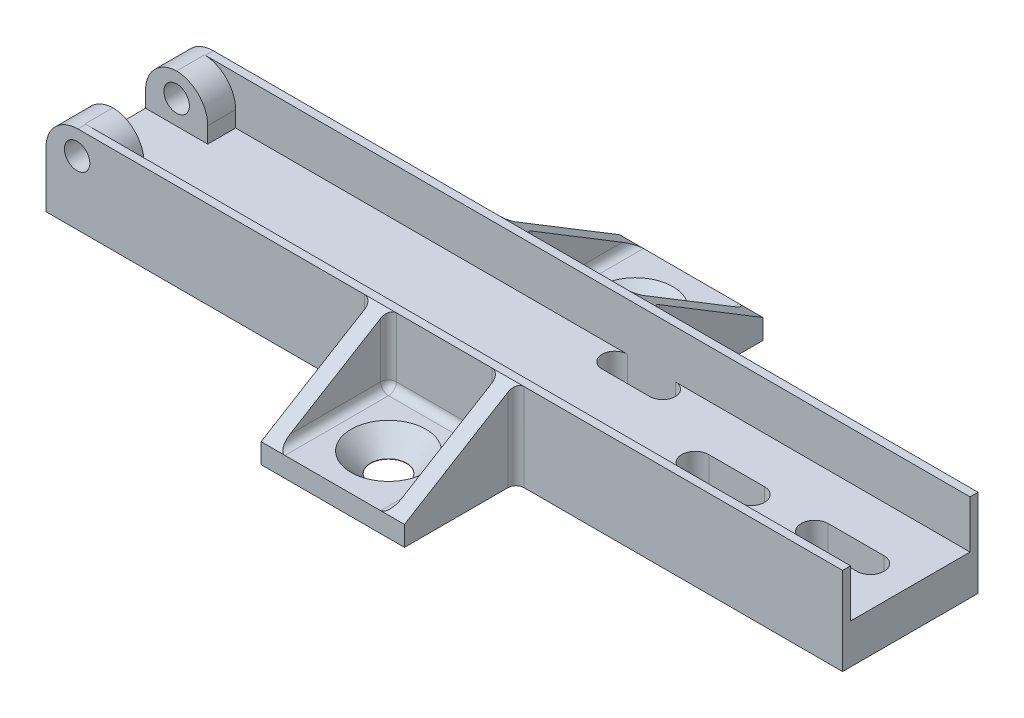
SolidWorks part; units mm, degrees
ref_plane "Ebene vorne" through (0, 0, 0) normal (0, 0, 1) x (1, 0, 0)
ref_plane "Ebene oben" through (0, 0, 0) normal (0, 1, 0) x (1, 0, 0)
ref_plane "Ebene rechts" through (0, 0, 0) normal (1, 0, 0) x (0, 0, -1)
sketch "Sketch1" plane through (0, 0, 0) normal (0, 1, 0) x (1, 0, 0)
  line L0 (-50, -7.5) -> (-50, 7.5)
  line L1 (-50, -7.5) -> (50, -7.5)
  line L2 (-50, 7.5) -> (50, 7.5)
  line L3 (50, -7.5) -> (50, 7.5)
  line L4 (-50, -7.5) -> (50, 7.5) construction
  line L5 (-50, 7.5) -> (50, -7.5) construction
  point P1 (0, 0)
  dimension "D1" = 15
  dimension "D2" = 100
extrude "Boss-Extrude1" add sketch "Sketch1" along normal blind 5
sketch "Sketch2" plane through (0, 5, 0) normal (0, 1, 0) x (1, 0, 0)
  line L0 (-50, -7.5) -> (50, -7.5) construction
  line L1 (-50, 7.5) -> (-42.1952, 7.5)
  line L2 (-50, 7.5) -> (-50, -7.5)
  line L3 (-50, -7.5) -> (-42.1952, -7.5)
  line L4 (-42.1952, 7.5) -> (-42.1952, -7.5)
extrude "Boss-Extrude2" add sketch "Sketch2" along normal blind 6
fillet "Fillet1" radius 4 1 edges at (-42.1952, 11, 0)
sketch "Sketch4" plane through (0, 11, 0) normal (0, 1, 0) x (1, 0, 0)
  line L0 (-42.1952, 0) -> (-50, 0) construction
  line L1 (-42.1952, -7.5) -> (-42.1952, 7.5) construction
  line L2 (-50, 7.5) -> (-50, -7.5) construction
  line L3 (-50, -4) -> (-42.1952, -4)
  line L4 (-50, -4) -> (-50, 4)
  line L5 (-42.1952, -4) -> (-42.1952, 4)
  line L6 (-50, 4) -> (-42.1952, 4)
  line L7 (-50, -4) -> (-42.1952, 4) construction
  line L8 (-42.1952, -4) -> (-50, 4) construction
  point P7 (-46.0976, 0)
  dimension "D1" = 8
extrude "Cut-Extrude2" cut sketch "Sketch4" against normal up to surface (6 mm away) up to face at (3.9024, 5, 0)
sketch "Sketch5" plane through (0, 0, 0) normal (0, -1, 0) x (1, 0, 0)
  line L0 (45, 0) -> (38, 0) construction
  line L1 (45, -1.7) -> (38, -1.7)
  line L2 (45, 1.7) -> (38, 1.7)
  line L3 (30, 0) -> (23, 0) construction
  line L4 (30, -1.7) -> (23, -1.7)
  line L5 (30, 1.7) -> (23, 1.7)
  line L7 (50, 7.5) -> (50, -7.5) construction
  arc A0 (45, -1.7) -> (45, 1.7) centre (45, 0) ccw
  arc A1 (38, 1.7) -> (38, -1.7) centre (38, 0) ccw
  arc A2 (30, -1.7) -> (30, 1.7) centre (30, 0) ccw
  arc A3 (23, 1.7) -> (23, -1.7) centre (23, 0) ccw
  point P3 (41.5, 0)
  point P8 (26.5, 0)
  dimension "D2" = 15
  dimension "^3,4" = 3.4
  dimension "D3" = 3.4
  dimension "D4" = 5
  dimension "D5" = 7
  dimension "D6" = 7
extrude "Cut-Extrude3" cut sketch "Sketch5" against normal up to surface (5 mm away) up to face at (-21.0976, 5, 0)
sketch "Sketch6" plane through (0, 5, 0) normal (0, 1, 0) x (1, 0, 0)
  line L0 (-50, 4) -> (-50, -4) construction
  line L1 (-26, 7.5) -> (-26, -7.5) construction
  line L2 (50, 7.5) -> (-42.1952, 7.5) construction
  line L3 (-42.1952, -7.5) -> (50, -7.5) construction
  circle A0 centre (-26, 0) radius 2.5
  point P10 (-26, 0)
  dimension "D1" = 5
  dimension "D2" = 24
extrude "Boss-Extrude3" [suppressed] add sketch "Sketch6" along normal blind 15
sketch "Sketch8" plane through (0, 0, 7.5) normal (0, 0, 1) x (1, 0, 0)
  line L1 (50, 0) -> (-50, 0)
  line L2 (50, 0) -> (50, 11)
  line L3 (50, 11) -> (-50, 11)
  line L4 (-50, 0) -> (-50, 11)
extrude "Boss-Extrude5" add sketch "Sketch8" along normal blind 1
mirror "Mirror1" about plane through (0, 0, 0) normal (0, 0, 1) of "Boss-Extrude5"
sketch "Sketch3" plane through (0, 0, 8.5) normal (0, 0, 1) x (1, 0, 0)
  line L0 (-42.1952, 7) -> (-42.1952, 5) construction
  line L1 (-42.1952, 8) -> (-50, 8) construction
  line L4 (-42.1952, 7) -> (-42.1952, 5) construction
  line L5 (-42.1952, 5) -> (-42.1952, 11) construction
  line L6 (50, 11) -> (-50, 11) construction
  line L7 (-50, 11) -> (-50, 0) construction
  circle A0 centre (-46.0976, 8) radius 1.6
  arc A1 (-42.1952, 7) -> (-46.1952, 11) centre (-46.1952, 7) ccw construction
  arc A2 (-42.1952, 7) -> (-46.1952, 11) centre (-46.1952, 7) ccw construction
  point P4 (0, 0)
  point P5 (0, 0)
  point P6 (0, 0)
  point P11 (0, 0)
  dimension "D1" = 3.2
extrude "Cut-Extrude1" cut sketch "Sketch3" against normal through all
fillet "Fillet2" radius 4 2 edges at (-50, 11, 6.25) (-50, 11, -6.25)
sketch "Sketch9" plane through (0, 0, 8.5) normal (0, 0, 1) x (1, 0, 0)
  line L0 (-50, 0) -> (50, 0) construction
  line L1 (-9, 0) -> (9, 0)
  line L2 (-9, 0) -> (-9, 2.5)
  line L3 (-9, 2.5) -> (9, 2.5)
  line L4 (9, 0) -> (9, 2.5)
  dimension "D1" = 2.5
  dimension "D2" = 18
extrude "Boss-Extrude6" add sketch "Sketch9" along normal blind 14
ref_plane "Plane1" through (0, 0, 0) normal (-1, 0, 0) x (0, 0, 1)
sketch "Sketch10" plane through (9, 0, 0) normal (1, 0, 0) x (0, 0, -1)
  line L0 (-8.5, 11) -> (-22.5, 2.5)
  line L1 (-22.5, 2.5) -> (-8.5, 2.5) construction
  line L2 (-22.5, 2.5) -> (-8.5, 2.5)
  line L3 (-8.5, 0) -> (-8.5, 11) construction
  line L4 (-8.5, 2.5) -> (-8.5, 11)
extrude "Boss-Extrude7" add sketch "Sketch10" against normal blind 2
mirror "Mirror2" about plane through (0, 0, 0) normal (-1, 0, 0) of "Boss-Extrude7"
hole_wizard "CSK for M4 Countersunk Flat Head Screw1" positions "Sketch13" profile "Sketch12" countersink size "M4" standard "DIN" end condition up to next
sketch "Sketch13" plane through (0, 2.5, 0) normal (0, 1, 0) x (1, 0, 0)
  line L0 (7, -15.5) -> (-7, -15.5) construction
  line L1 (7, -22.5) -> (7, -8.5) construction
  line L2 (-7, -22.5) -> (-7, -8.5) construction
  point P9 (0, -15.5)
sketch "Sketch12" plane through (0, 2.5, 15.5) normal (1, 0, 0) x (0, 0, 1)
  line L0 (0, 0) -> (0, 2.501)
  line L1 (0, 2.501) -> (2.25, 2.501)
  line L2 (2.25, 2.501) -> (2.25, 2.45)
  line L3 (2.25, 2.45) -> (4.7, 0)
  line L5 (4.7, 0) -> (0, 0)
  line L6 (-2.25, 2.45) -> (-4.7, 0) construction
  line L11 (0, -6.35) -> (0, 107.95) construction
  dimension "Thru Hole Dia." = 4.5
  dimension "Thru Hole Depth" = 2.501
  dimension "Near C'Sink Dia." = 9.4
  dimension "Near C'Sink Angle" = 90
mirror "Mirror5" about plane through (0, 0, 0) normal (0, 0, 1) of "CSK for M4 Countersunk Flat Head Screw1", "Mirror2", "Boss-Extrude7", "Boss-Extrude6"
fillet "Fillet4" radius 1 14 edges at (-7, 6.75, 8.5) (7, 6.75, 8.5) (9, 5.5, 8.5) (-9, 5.5, 8.5) (-7, 2.5, 15.5) (7, 2.5, 15.5) (0, 2.5, 8.5) (9, 5.5, -8.5) (-9, 5.5, -8.5) (7, 6.75, -8.5) (-7, 6.75, -8.5) (0, 2.5, -8.5) (-7, 2.5, -15.5) (7, 2.5, -15.5)
sketch "Sketch14" plane through (0, 5, 0) normal (0, 1, 0) x (1, 0, 0)
  line L0 (13, -5.9) -> (7, -5.9) construction
  line L1 (13, -7.5) -> (7, -7.5)
  line L2 (13, -4.3) -> (7, -4.3)
  line L3 (-42.1952, -7.5) -> (50, -7.5) construction
  line L4 (0, 0) -> (19.2609, 0) construction
  line L5 (13, 5.9) -> (7, 5.9) construction
  line L6 (13, 7.5) -> (7, 7.5)
  line L7 (13, 4.3) -> (7, 4.3)
  arc A0 (13, -7.5) -> (13, -4.3) centre (13, -5.9) ccw
  arc A1 (7, -4.3) -> (7, -7.5) centre (7, -5.9) ccw
  arc A2 (13, 7.5) -> (13, 4.3) centre (13, 5.9) cw
  arc A3 (7, 4.3) -> (7, 7.5) centre (7, 5.9) cw
  point P2 (10, -5.9)
  point P14 (10, 5.9)
  dimension "D1" = 10
  dimension "D2" = 6
  dimension "D3" = 3.2
extrude "Cut-Extrude4" cut sketch "Sketch14" against normal up to next
chamfer "Chamfer1" distance 1 angle 45 16 edges at (10, 0, -4.3) (5.4, 0, -5.9) (14.6, 0, -5.9) (10, 0, -7.5) (10, 0, 7.5) (5.4, 0, 5.9) (14.6, 0, 5.9) (10, 0, 4.3) (26.5, 0, 1.7) (21.3, 0, 0) (31.7, 0, 0) (26.5, 0, -1.7) (41.5, 0, 1.7) (36.3, 0, 0) (46.7, 0, 0) (41.5, 0, -1.7)
